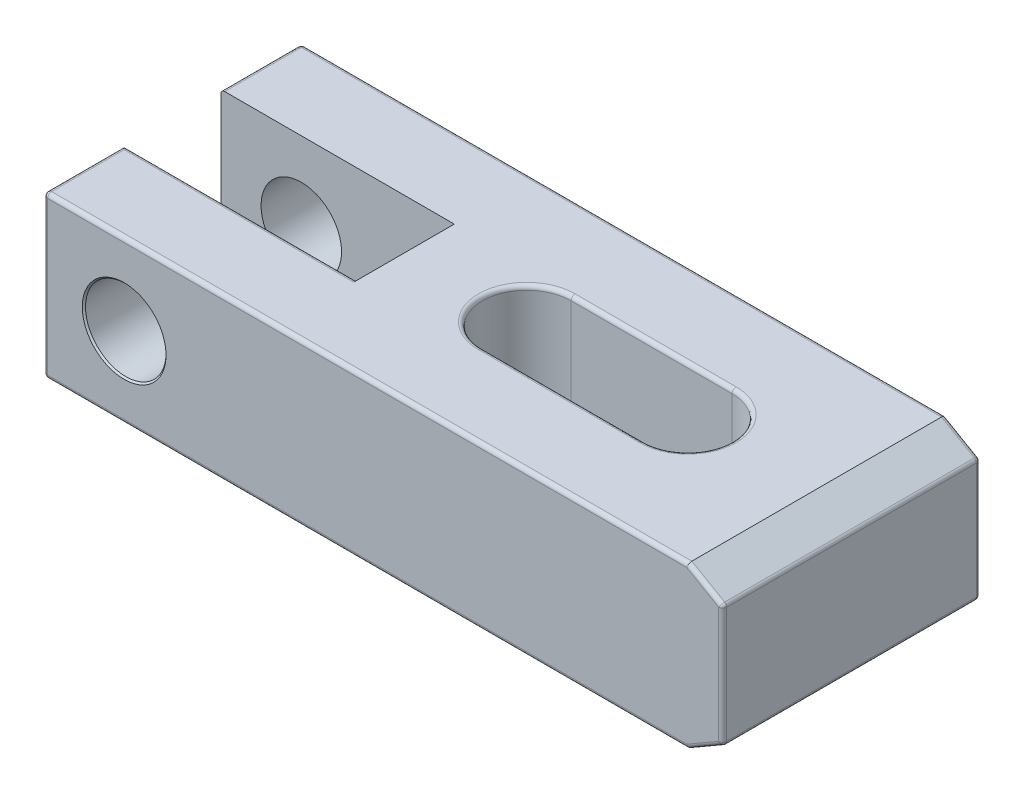
SolidWorks part; units mm, degrees
ref_plane "Front Plane" through (0, 0, 0) normal (0, 0, 1) x (1, 0, 0)
ref_plane "Top Plane" through (0, 0, 0) normal (0, 1, 0) x (1, 0, 0)
ref_plane "Right Plane" through (0, 0, 0) normal (1, 0, 0) x (0, 0, -1)
other "base-bride"
sketch "esquisse_base_bride" plane through (0, 0, 0) normal (0, 0, 1) x (1, 0, 0)
  line L0 (40, 10) -> (44.3301, 7.5)
  line L1 (-40, -10) -> (40, -10)
  line L2 (-40, -10) -> (-40, 10)
  line L3 (-40, 10) -> (40, 10)
  line L4 (44.3301, -7.5) -> (44.3301, 7.5)
  line L6 (44.3301, -7.5) -> (40, -10)
  dimension "D1" = 60
  dimension "D2" = 40
  dimension "D3" = 80
  dimension "D4" = 20
  dimension "D5" = 15
  dimension "D6" = 10
extrude "Base_bride" add sketch "esquisse_base_bride" along normal blind 32
fillet "congé_bride1" radius 0.5 16 edges at (-40, 10, 16) (-40, -10, 16) (0, -10, 0) (42.1651, -8.75, 0) (42.1651, 8.75, 0) (0, 10, 0) (-40, 0, 0) (44.3301, -7.5, 16) (44.3301, 7.5, 16) (44.3301, 0, 0) (0, 10, 32) (42.1651, 8.75, 32) (44.3301, 0, 32) (42.1651, -8.75, 32) (0, -10, 32) (-40, 0, 32)
sketch "esquisse_enlèv.mat.brid" plane through (0, 10, 0) normal (0, 1, 0) x (1, 0, 0)
  line L0 (-1039.5, -16) -> (48960.5, -16) construction
  line L1 (-39.5, -0.5) -> (-39.5, -31.5) construction
  line L2 (-40, -31.5) -> (-40, -0.5) construction
  line L3 (-40, -10) -> (-11, -10)
  line L4 (-40, -10) -> (-40, -22)
  line L5 (-40, -22) -> (-11, -22)
  line L6 (-11, -10) -> (-11, -22)
  line L7 (4, -16) -> (24, -16) construction
  line L8 (4, -10.5) -> (24, -10.5)
  line L9 (4, -21.5) -> (24, -21.5)
  arc A0 (4, -10.5) -> (4, -21.5) centre (4, -16) ccw
  arc A1 (24, -21.5) -> (24, -10.5) centre (24, -16) ccw
  point P5 (-39.5, -16)
  point P11 (-11, -16)
  point P14 (14, -16)
  point P18 (29.5, -16)
  dimension "D5" = 15
  dimension "D3" = 20
  dimension "D4" = 5.5
  dimension "D1" = 12
  dimension "D2" = 29
extrude "enlèv.matière_bride" cut sketch "esquisse_enlèv.mat.brid" against normal through all
fillet "congé_bride2" radius 0.5 10 edges at (-25.25, -10, 22) (-25.25, 10, 22) (29.5, 10, 16) (14, 10, 10.5) (-1.5, 10, 16) (14, 10, 21.5) (29.5, -10, 16) (14, -10, 10.5) (-1.5, -10, 16) (14, -10, 21.5) tangent propagation no
sketch "esquisse_percage_bride" plane through (0, 0, 32) normal (0, 0, 1) x (1, 0, 0)
  line L0 (-40, -9.5) -> (-40, 9.5) construction
  line L1 (-39.5, 10) -> (40, 10) construction
  circle A0 centre (-30, 0) radius 5
  dimension "D1" = 10
  dimension "D2" = 10
  dimension "D3" = 10
extrude "percage_bride" cut sketch "esquisse_percage_bride" against normal through all
chamfer "chanfrein_bride" distance 0.2 angle 45 3 edges at (-25, 0, 22) (-25, 0, 32) (-25, 0, 0)
